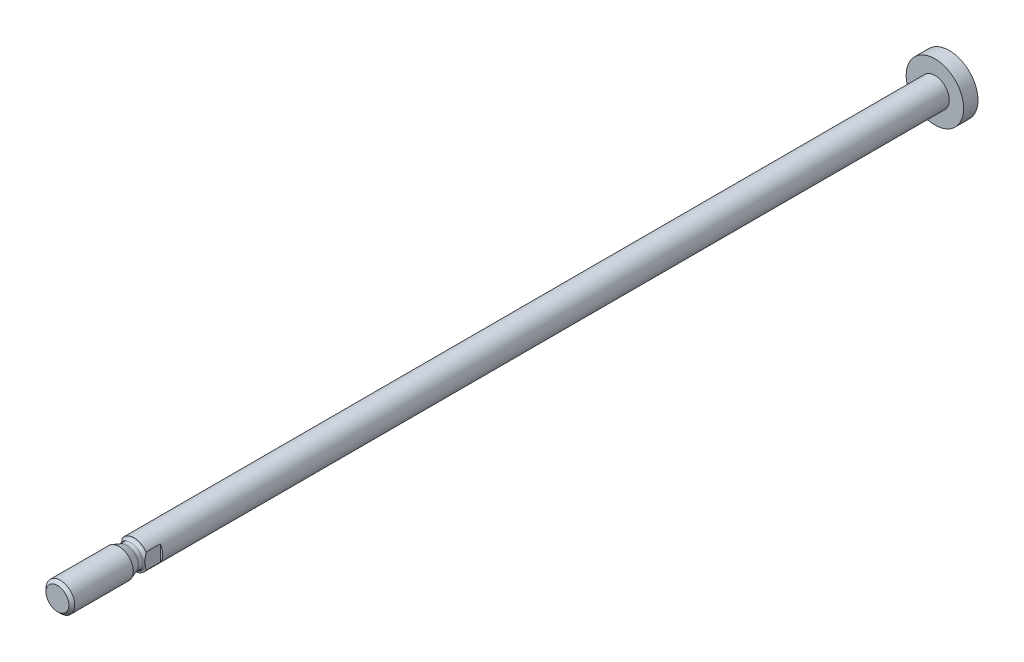
SolidWorks part; units mm, degrees
ref_plane "Ebene vorne" through (0, 0, 0) normal (0, 0, 1) x (1, 0, 0)
ref_plane "Ebene oben" through (0, 0, 0) normal (0, 1, 0) x (1, 0, 0)
ref_plane "Ebene rechts" through (0, 0, 0) normal (1, 0, 0) x (0, 0, -1)
sketch "Skizze1" plane through (0, 0, 0) normal (1, 0, 0) x (0, 0, -1)
  line L0 (-5, 0) -> (-5, 3)
  line L1 (-5, 3) -> (162.3, 3)
  line L2 (162.3, 3) -> (162.3, 6)
  line L3 (162.3, 6) -> (165.3, 6)
  line L4 (165.3, 6) -> (165.3, 0)
  line L5 (165.3, 0) -> (-5, 0)
  line L6 (165.3, 0) -> (-5, 0) construction
revolve "Rotation1" add sketch "Skizze1" angle 360 about L6 reverse direction yes
sketch "Skizze2" plane through (0, 0, 0) normal (1, 0, 0) x (0, 0, -1)
  line L0 (-21, 0) -> (-21, 2.3865)
  line L1 (-21, 2.3865) -> (-20.3865, 3)
  line L2 (-20.3865, 3) -> (-8.1485, 3)
  line L3 (-8.1485, 3) -> (-6.5994, 2.4362)
  line L4 (-6.3942, 2.4) -> (-5.6, 2.4)
  line L5 (-5, 3) -> (-4, 3)
  line L6 (-4, 3) -> (-4, 0)
  line L7 (-4, 0) -> (-21, 0)
  line L8 (-4, 0) -> (-21, 0) construction
  arc A0 (-6.5994, 2.4362) -> (-6.3942, 2.4) centre (-6.3942, 3) ccw
  arc A1 (-5.6, 2.4) -> (-5, 3) centre (-5.6, 3) ccw
revolve "Rotation2" add sketch "Skizze2" angle 360 about L8 reverse direction yes
cosmetic thread "Gewindedarstellung1" parameters "D1"=12.8515, "D2"=4.773
ref_plane "Ebene1" through (0, 0, 5) normal (0, 0, 1) x (1, 0, 0)
ref_plane "Ebene2" through (0, 0, 2) normal (0, 0, 1) x (1, 0, 0)
sketch "Skizze3" plane through (0, 0, 2) normal (0, 0, 1) x (1, 0, 0)
  line L0 (-5, 10) -> (-5, -5)
  line L1 (-5, -5) -> (-2.5, -5)
  line L2 (-2.5, -5) -> (-2.5, 5)
  line L3 (-2.5, 5) -> (2.5, 5)
  line L4 (2.5, 5) -> (2.5, -5)
  line L5 (2.5, -5) -> (5, -5)
  line L6 (5, -5) -> (5, 10)
  line L7 (5, 10) -> (-5, 10)
extrude "Schnitt-Linear austragen1" cut sketch "Skizze3" along normal blind 4
ref_plane "Ebene3" through (0, 0, -339) normal (0, 0, 1) x (1, 0, 0)
ref_plane "Ebene4" through (0, 0, 16) normal (0, 0, 1) x (1, 0, 0)
ref_plane "Ebene5" through (0, 0, 11.2) normal (0, 0, 1) x (1, 0, 0)
ref_plane "FDT_KSAUFSATZ XY" through (0, 0, 11.2) normal (0, 0, 1) x (1, 0, 0)
ref_plane "FDT_KSAUFSATZ XZ" through (0, 0, 0) normal (0, 1, 0) x (1, 0, 0)
ref_plane "FDT_KSAUFSATZ YZ" through (0, 0, 0) normal (-1, 0, 0) x (0, 0, 1)
ref_axis "FDT_KSAUFSATZ X" through (80.9, 0, 11.2) along (-1, 0, 0)
ref_axis "FDT_KSAUFSATZ Y" through (0, 50, 11.2) along (0, -1, 0)
ref_axis "FDT_KSAUFSATZ Z" through (0, 0, 80.9) along (0, 0, -1)
sketch3d "FDT_KSAUFSATZ"
  point P0 (0, 0, 11.2)
ref_plane "FDT_NUT XY" through (0, 0, 11.2) normal (0, 0, 1) x (1, 0, 0)
ref_plane "FDT_NUT XZ" through (0, 0, 0) normal (0, 1, 0) x (1, 0, 0)
ref_plane "FDT_NUT YZ" through (0, 0, 0) normal (-1, 0, 0) x (0, 0, 1)
ref_axis "FDT_NUT X" through (80.9, 0, 11.2) along (-1, 0, 0)
ref_axis "FDT_NUT Y" through (0, 50, 11.2) along (0, -1, 0)
ref_axis "FDT_NUT Z" through (0, 0, 80.9) along (0, 0, -1)
sketch3d "FDT_NUT"
  point P0 (0, 0, 11.2)
ref_plane "KS XY" through (0, 0, 0) normal (0, 0, -1) x (-1, 0, 0)
ref_plane "KS XZ" through (0, 0, 0) normal (0, 1, 0) x (1, 0, 0)
ref_plane "KS YZ" through (0, 0, 0) normal (1, 0, 0) x (0, 0, -1)
ref_axis "KS X" through (-80.9, 0, 0) along (1, 0, 0)
ref_axis "KS Y" through (0, 50, 0) along (0, -1, 0)
ref_axis "KS Z" through (0, 0, -80.9) along (0, 0, 1)
sketch3d "KS"
  point P0 (0, 0, 0)
ref_plane "NUT1 XY" through (0, 0, 16) normal (0, 0, 1) x (1, 0, 0)
ref_plane "NUT1 XZ" through (0, 0, 0) normal (0, -1, 0) x (-1, 0, 0)
ref_plane "NUT1 YZ" through (0, 0, 0) normal (1, 0, 0) x (0, 0, -1)
ref_axis "NUT1 X" through (-80.9, 0, 16) along (1, 0, 0)
ref_axis "NUT1 Y" through (0, -50, 16) along (0, 1, 0)
ref_axis "NUT1 Z" through (0, 0, 80.9) along (0, 0, -1)
sketch3d "NUT1"
  point P0 (0, 0, 16)
